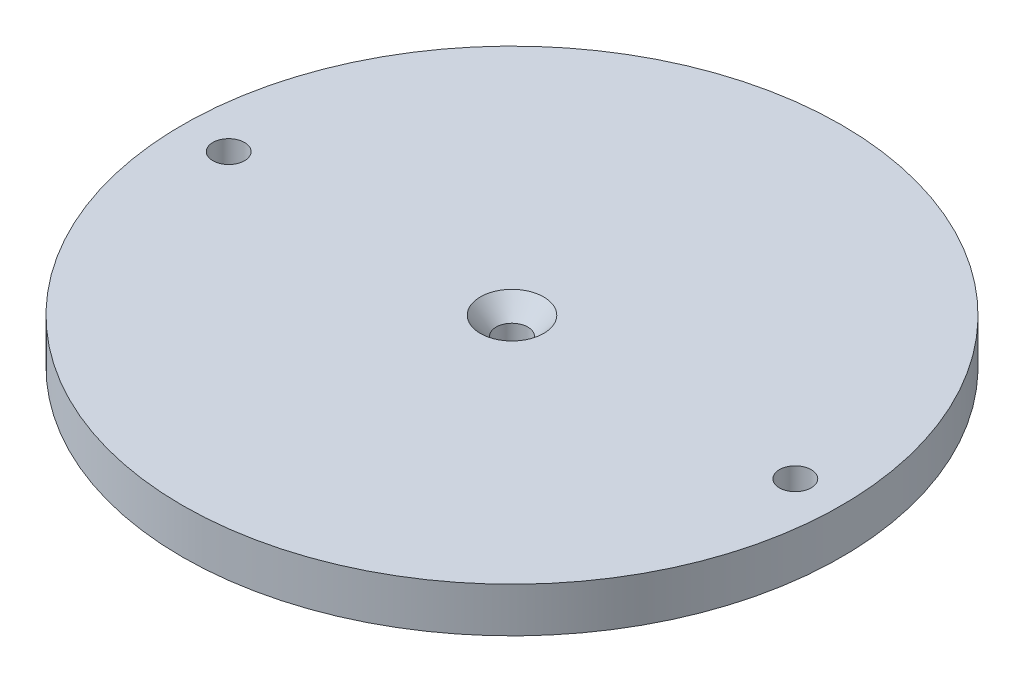
SolidWorks part; units mm, degrees
material "6061 Alloy"
ref_plane "Front Plane" through (0, 0, 0) normal (0, 0, 1) x (1, 0, 0)
ref_plane "Top Plane" through (0, 0, 0) normal (0, 1, 0) x (1, 0, 0)
ref_plane "Right Plane" through (0, 0, 0) normal (1, 0, 0) x (0, 0, -1)
sketch "Sketch2" plane through (0, 0, 0) normal (0, 1, 0) x (1, 0, 0)
  circle A0 centre (0, 0) radius 70.1675
  dimension "D1" = 140.335
extrude "Boss-Extrude1" add sketch "Sketch2" along normal blind 9.525
sketch "Sketch3" plane through (0, 9.525, 0) normal (0, 1, 0) x (1, 0, 0)
  point P0 (-60.325, 0)
  point P1 (60.325, 0)
  dimension "D1" = 60.325
  dimension "D2" = 60.325
hole_wizard "1/4 Clearance Hole1" positions "Sketch3" profile "Sketch4" hole size "1/4" standard "ANSI Inch" end condition through all
sketch "Sketch4" plane through (-60.325, 9.525, 0) normal (1, 0, 0) x (0, 0, 1)
  line L0 (0, 0) -> (0, 9.525)
  line L1 (0, 9.525) -> (3.3782, 9.525)
  line L2 (3.3782, 9.525) -> (3.3782, 0)
  line L5 (3.3782, 0) -> (0, 0)
  line L11 (0, -6.35) -> (0, 107.95) construction
  dimension "Thru Hole Dia." = 6.7564
  dimension "Thru Hole Depth" = 9.525
sketch "Sketch5" plane through (0, 9.525, 0) normal (0, 1, 0) x (1, 0, 0)
  point P0 (0, 0)
hole_wizard "CSK for 1/4 Flat Head Machine Screw1" positions "Sketch5" profile "Sketch7" countersink size "1/4" standard "ANSI Inch" end condition through all
sketch "Sketch7" plane through (0, 9.525, 0) normal (1, 0, 0) x (0, 0, 1)
  line L0 (0, 0) -> (0, 9.525)
  line L1 (0, 9.525) -> (3.3782, 9.525)
  line L2 (3.3782, 9.525) -> (3.3782, 3.8716)
  line L3 (3.3782, 3.8716) -> (6.7437, 0)
  line L5 (6.7437, 0) -> (0, 0)
  line L6 (-3.3782, 3.8716) -> (-6.7437, 0) construction
  line L11 (0, -6.35) -> (0, 107.95) construction
  dimension "Thru Hole Dia." = 6.7564
  dimension "Thru Hole Depth" = 9.525
  dimension "Near C'Sink Dia." = 13.4874
  dimension "Near C'Sink Angle" = 82
equation "\"outerdiameter\" = 5.525"
equation "\"platethickness\"= 0.375"
equation "\"holespacing\"= 2.375"
equation "\"D1@Sketch2\"=\"outerdiameter\""
equation "\"D1@Boss-Extrude1\"=\"platethickness\""
equation "\"D2@Sketch3\"=\"holespacing\""
equation "\"D1@Sketch3\"=\"holespacing\""
